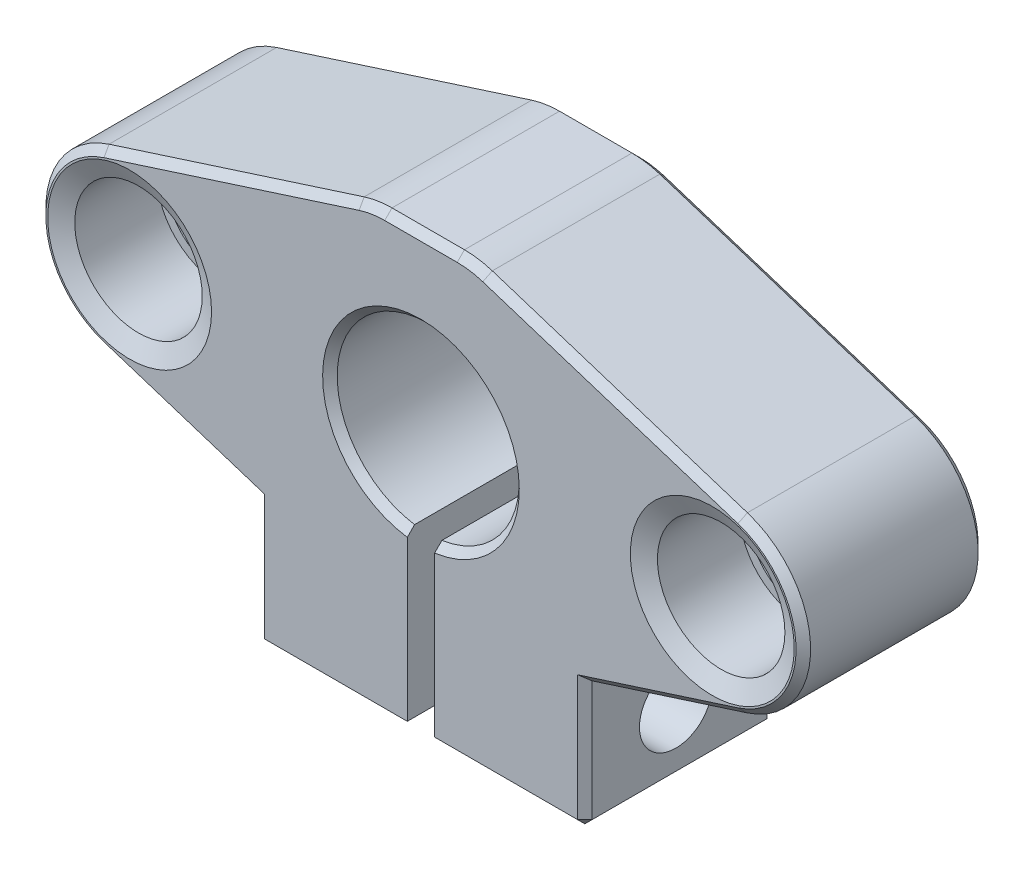
SolidWorks part; units mm, degrees
ref_plane "Front Plane" through (0, 0, 0) normal (0, 0, 1) x (1, 0, 0)
ref_plane "Top Plane" through (0, 0, 0) normal (0, 1, 0) x (1, 0, 0)
ref_plane "Right Plane" through (0, 0, 0) normal (1, 0, 0) x (0, 0, -1)
ref_plane "Plane1" through (0, 0, 10) normal (0, 0, 1) x (1, 0, 0)
sketch "Sketch1" plane through (0, 0, 10) normal (0, 0, 1) x (1, 0, 0)
  line L0 (-9, -7.5) -> (-9, -14.5)
  line L1 (-9, -14.5) -> (9, -14.5)
  line L2 (9, -14.5) -> (9, -7.5)
  line L3 (9, -7.5) -> (17.5291, -4.7605)
  line L4 (17.5291, 4.7605) -> (2.7734, 9.5)
  line L5 (2.7734, 9.5) -> (-2.7734, 9.5)
  line L6 (-2.7734, 9.5) -> (-17.5291, 4.7605)
  line L7 (-17.5291, -4.7605) -> (-9, -7.5)
  arc A0 (17.5291, -4.7605) -> (17.5291, 4.7605) centre (16, 0) ccw
  arc A1 (-17.5291, 4.7605) -> (-17.5291, -4.7605) centre (-16, 0) ccw
extrude "Boss-Extrude1" add sketch "Sketch1" against normal blind 10
sketch "Sketch2" plane through (0, 0, 0) normal (0, 0, -1) x (-1, 0, 0)
  line L0 (9, -11.2309) -> (9, -10.7691)
  line L1 (9, -10.7691) -> (8.2, -10.7691)
  line L2 (8.2, -10.7691) -> (9, -11.2309)
extrude "Cut-Extrude1" cut sketch "Sketch2" against normal through all
sketch "Sketch3" plane through (0, 0, 0) normal (0, 0, -1) x (-1, 0, 0)
  line L0 (0.75, -14.5) -> (0.75, -4.9434)
  line L1 (-0.75, -4.9434) -> (-0.75, -14.5)
  line L2 (-0.75, -14.5) -> (0.75, -14.5)
  arc A0 (0.75, -4.9434) -> (-0.75, -4.9434) centre (0, 0) cw
extrude "Cut-Extrude2" cut sketch "Sketch3" against normal through all
draft "Draft1" type of draft neutral plane draft angle 30 faces to draft 1 face at (-8.6, -10.7691, 5) neutral plane through (-9, -7.5, 0) neutral plane normal (-1, 0, 0) parameters "D1"=30
ref_plane "Plane2" through (0, 0, 0) normal (0, -1, 0) x (1, 0, 0)
sketch "Sketch4" plane through (0, 0, 0) normal (0, -1, 0) x (1, 0, 0)
  line L0 (5, 10) -> (0, 10)
  line L1 (0, 10) -> (0, 0)
  line L2 (0, 0) -> (5, 0)
  line L3 (5, 0) -> (5, 10)
  line L4 (0, 10) -> (0, 0) construction
revolve "Cut-Revolve1" cut sketch "Sketch4" angle 360 about L4 reverse direction yes
hole_wizard "Ø4.0 (4) Diameter Hole1" positions "Sketch6" profile "Sketch5" hole size "Ø4.0" standard "ANSI Metric"
sketch "Sketch6" plane through (-0.75, 0, 0) normal (1, 0, 0) x (0, 0, -1)
  point P0 (-5, -11)
sketch "Sketch5" plane through (-0.75, -11, 5) normal (0, 1, 0) x (0, 0, -1)
  line L0 (0, 0) -> (0, 20.25)
  line L1 (0, 20.25) -> (2, 20.25)
  line L2 (2, 20.25) -> (2, 0)
  line L5 (2, 0) -> (0, 0)
  line L11 (0, -6.35) -> (0, 107.95) construction
  dimension "Thru Hole Dia." = 4
  dimension "Thru Hole Depth" = 20.25
hole_wizard "Ø4.0 (4) Diameter Hole2" positions "Sketch8" profile "Sketch7" hole size "Ø4.0" standard "ANSI Metric"
sketch "Sketch8" plane through (0.75, 0, 0) normal (-1, 0, 0) x (0, 0, 1)
  point P0 (5, -11)
sketch "Sketch7" plane through (0.75, -11, 5) normal (0, 1, 0) x (0, 0, 1)
  line L0 (0, 0) -> (0, 20.25)
  line L1 (0, 20.25) -> (2, 20.25)
  line L2 (2, 20.25) -> (2, 0)
  line L5 (2, 0) -> (0, 0)
  line L11 (0, -6.35) -> (0, 107.95) construction
  dimension "Thru Hole Dia." = 4
  dimension "Thru Hole Depth" = 20.25
hole_wizard "M7x1.0 Tapped Hole1" positions "Sketch10" profile "Sketch9" tap size "M7x1.0" standard "ANSI Metric"
sketch "Sketch10" plane through (0, 0, 10) normal (0, 0, 1) x (1, 0, 0)
  point P0 (-16, 0)
  point P1 (16, 0)
sketch "Sketch9" plane through (-16, 0, 10) normal (1, 0, 0) x (0, -1, 0)
  line L0 (0, 0) -> (0, 10)
  line L1 (0, 10) -> (3, 10)
  line L3 (3, 10) -> (3, 5)
  line L4 (3, 5) -> (3.5, 5)
  line L5 (3.5, 5) -> (3.5, 0)
  line L7 (3.5, 0) -> (0, 0)
  line L11 (0, -6.35) -> (0, 107.95) construction
  dimension "Thru Tap Drill Dia." = 6
  dimension "Thru Tap Drill Depth" = 10
  dimension "Thread Major Dia." = 7
  dimension "Thread Depth" = 5
fillet "Fillet1" radius 5 2 edges at (2.7734, 9.5, 5) (-2.7734, 9.5, 5) tangent propagation no
chamfer "Chamfer1" distance 1 angle 26 2 edges at (19.5, 0, 10) (-12.5, 0, 10) first distance on face at (-12.5, 0, 10)
chamfer "Chamfer2" distance 0.4 angle 45 31 edges at (13.2645, -6.1302, 0) (21, 0, 0) (10.5241, 7.0105, 0) (2.7639, 9.4398, 0) (0, 9.5, 0) (-2.7639, 9.4398, 0) (-10.5241, 7.0105, 0) (-13.2645, -6.1302, 0) (-21, 0, 0) (-9, -9.1345, 10) (-13.2645, -6.1302, 10) (-21, 0, 10) (-10.5241, 7.0105, 10) (-2.7639, 9.4398, 10) (0, 9.5, 10) (2.7639, 9.4398, 10) (10.5241, 7.0105, 10) (21, 0, 10) (13.2645, -6.1302, 10) (9, -11, 10) (4.875, -14.5, 10) (9, -14.5, 5) (0.75, -14.5, 5) (4.875, -14.5, 0) (0, 5, 10) (-9, -12.8655, 10) (-9, -14.5, 5) (-4.875, -14.5, 0) (-0.75, -14.5, 5) (-4.875, -14.5, 10) (0, 5, 0)
chamfer "Chamfer3" distance 1 angle 26 2 edges at (-13, 0, 0) (19, 0, 0) first distance on face at (-13, 0, 0)
